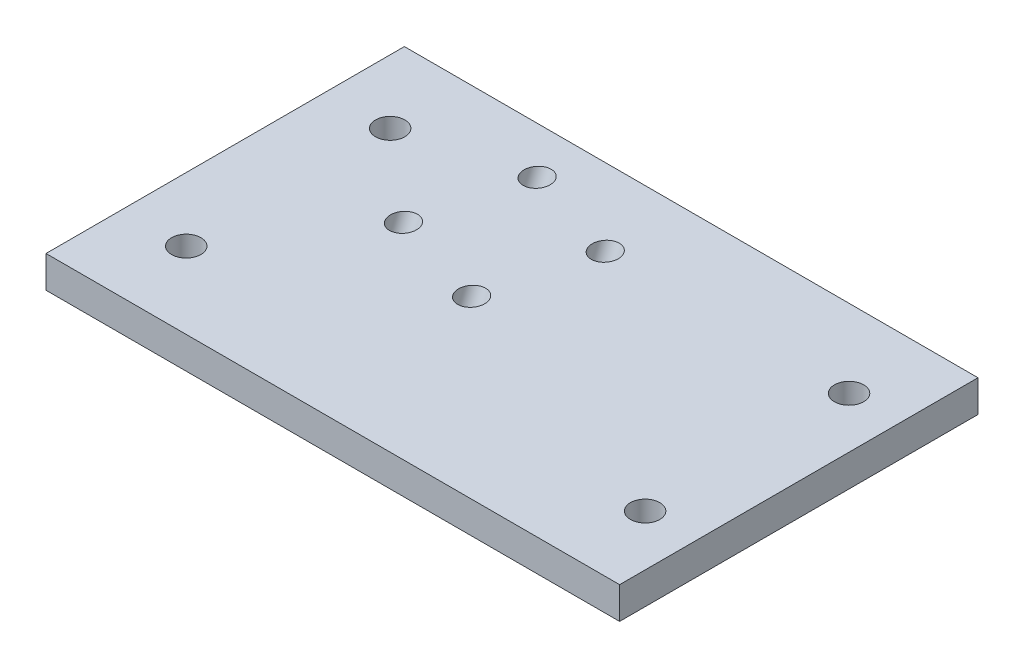
SolidWorks part; units mm, degrees
ref_plane "Front" through (0, 0, 0) normal (0, 0, 1) x (1, 0, 0)
ref_plane "Top" through (0, 0, 0) normal (0, 1, 0) x (1, 0, 0)
ref_plane "Right" through (0, 0, 0) normal (1, 0, 0) x (0, 0, -1)
sketch "Sketch1" plane through (0, 0, 0) normal (0, 1, 0) x (1, 0, 0)
  line L1 (0, 0) -> (90, 0)
  line L2 (0, 0) -> (0, 56.23)
  line L3 (0, 56.23) -> (90, 56.23)
  line L4 (90, 0) -> (90, 56.23)
  dimension "D1" = 90
  dimension "D2" = 56.23
extrude "Boss-Extrude1" add sketch "Sketch1" along normal blind 5
sketch "Sketch2" plane through (0, 5, 0) normal (0, 1, 0) x (1, 0, 0)
  circle A0 centre (82, 12) radius 2.3
  circle A1 centre (10, 12) radius 2.3
extrude "Cut-Extrude1" cut sketch "Sketch2" against normal blind 15
sketch "Sketch4" plane through (0, 5, 0) normal (0, 1, 0) x (1, 0, 0)
  circle A0 centre (39.2121, 27.5705) radius 2.204
  circle A1 centre (23.8176, 32.2728) radius 4.0674
  circle A2 centre (43.572, 44.174) radius 17.6111
  circle A3 centre (28.1775, 48.8763) radius 2.2
ref_plane "Plane1" through (0, 23.8287, -9.6274) normal (0, 0.9272, -0.3746) x (-1, 0, 0)
sketch "Sketch6" plane through (0, 23.8287, -9.6274) normal (0, 0.9272, -0.3746) x (-1, 0, 0)
  circle A0 centre (-28.1775, -43.4443) radius 2.0398
  circle A1 centre (-23.8176, -28.0498) radius 2.0398
  circle A2 centre (-39.2121, -23.6899) radius 2.0398
  circle A3 centre (-43.572, -39.0844) radius 2.0398
extrude "Cut-Extrude2" cut sketch "Sketch6" against normal blind 45
sketch "Sketch7" plane through (0, 5, 0) normal (0, 1, 0) x (1, 0, 0)
  circle A0 centre (82, 44) radius 2.3
  circle A1 centre (10, 44) radius 2.3
extrude "Cut-Extrude3" cut sketch "Sketch7" against normal blind 45
